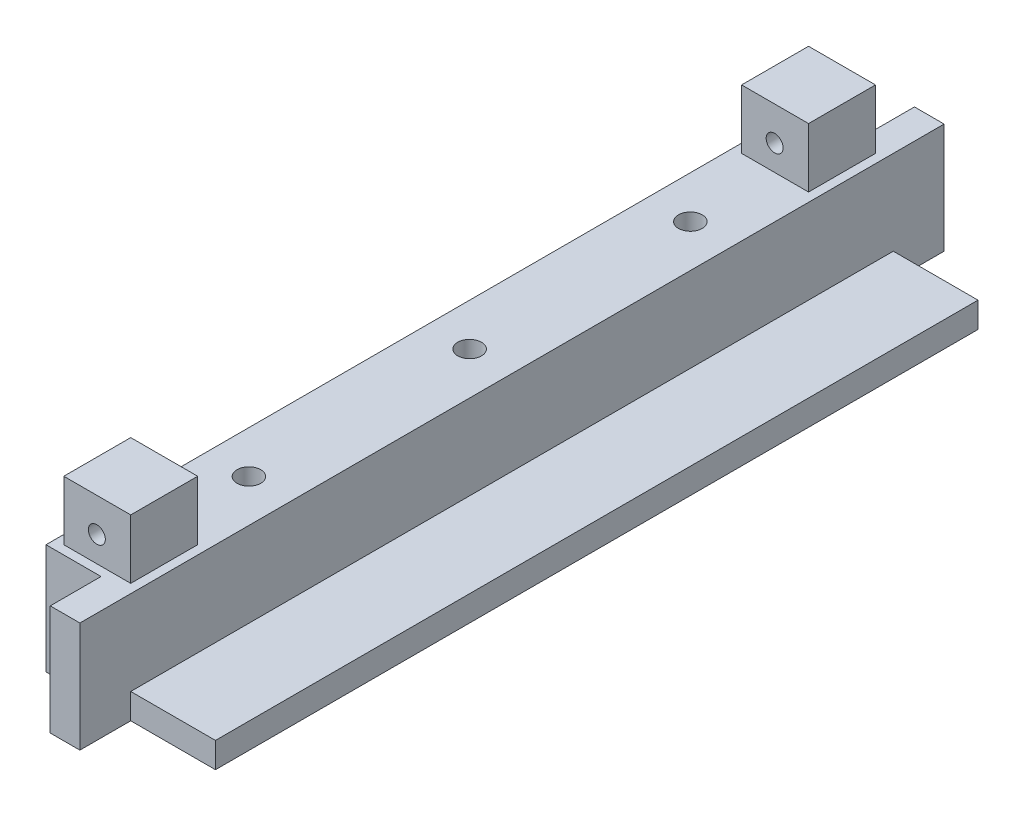
SolidWorks part; units mm, degrees
ref_plane "Płaszczyzna przednia" through (0, 0, 0) normal (0, 0, 1) x (1, 0, 0)
ref_plane "Płaszczyzna górna" through (0, 0, 0) normal (0, 1, 0) x (1, 0, 0)
ref_plane "Płaszczyzna prawa" through (0, 0, 0) normal (1, 0, 0) x (0, 0, -1)
sketch "Szkic1" plane through (0, 0, 0) normal (0, 0, 1) x (1, 0, 0)
  line L0 (10, -10) -> (10, -16)
  line L1 (-10, -10) -> (10, -10)
  line L2 (-10, -10) -> (-10, 10)
  line L3 (-10, 10) -> (10, 10)
  line L4 (10, -10) -> (10, 10)
  line L5 (-10, -10) -> (10, 10) construction
  line L6 (-10, 10) -> (10, -10) construction
  line L7 (10, -16) -> (-30, -16)
  line L8 (-30, -16) -> (-30, 10)
  line L9 (-30, 10) -> (-10, 10)
  point P0 (0, 0)
  dimension "D1" = 20
  dimension "D2" = 40
  dimension "D3" = 6
extrude "Dodanie-wyciągnięcie1" add sketch "Szkic1" along normal blind 180 contours L8 L7 L0 L1 L2 L3 region at (-16.25, -4.875, 0)
sketch "Szkic2" plane through (0, 10, 0) normal (0, 1, 0) x (1, 0, 0)
  line L0 (-30, -180) -> (-30, 0) construction
  line L1 (-12.1, -17.9) -> (-27.9, -17.9)
  line L2 (-12.1, -17.9) -> (-12.1, -2.1)
  line L3 (-12.1, -2.1) -> (-27.9, -2.1)
  line L4 (-27.9, -17.9) -> (-27.9, -2.1)
  line L5 (-12.1, -17.9) -> (-27.9, -2.1) construction
  line L6 (-12.1, -2.1) -> (-27.9, -17.9) construction
  line L7 (-30, 0) -> (-10, 0) construction
  point P0 (-20, -10)
  dimension "D1" = 15.8
  dimension "D2" = 15.8
  dimension "D3" = 10
  dimension "D4" = 10
extrude "Dodanie-wyciągnięcie2" add sketch "Szkic2" along normal blind 14
ref_plane "Płaszczyzna1" through (0, 0, 90) normal (0, 0, 1) x (1, 0, 0)
mirror "Lustro1" about plane through (0, 0, 90) normal (0, 0, 1) of "Dodanie-wyciągnięcie2"
sketch "Szkic5" plane through (0, 10, 0) normal (0, 1, 0) x (1, 0, 0)
  line L1 (-30, -180) -> (-10, -180) construction
  line L2 (-27.9, -162.1) -> (-12.1, -162.1) construction
  line L3 (-27.9, -17.9) -> (-12.1, -17.9) construction
  line L4 (-30, -180) -> (-30, 0) construction
  circle A0 centre (-20, -142.1) radius 2.8
  circle A1 centre (-20, -90) radius 2.8
  circle A2 centre (-20, -37.9) radius 2.8
  point P11 (-20, -180)
  point P17 (-30, -90)
  dimension "D1" = 5.6
  dimension "D4" = 20
  dimension "D5" = 20
extrude "Wytnij-wyciągnięcie2" cut sketch "Szkic5" against normal blind 10
sketch "Szkic6" plane through (0, 0, 177.9) normal (0, 0, 1) x (1, 0, 0)
  line L0 (-12.1, 24) -> (-27.9, 24) construction
  line L1 (-12.1, 24) -> (-12.1, 10) construction
  circle A0 centre (-20.1, 16) radius 2
  dimension "D1" = 4
  dimension "D2" = 8
  dimension "D3" = 8
extrude "Wytnij-wyciągnięcie3" cut sketch "Szkic6" against normal through all
sketch "Szkic9" plane through (0, 0, 180) normal (0, 0, 1) x (1, 0, 0)
  line L1 (-10, 10) -> (-17, 10)
  line L2 (-10, 10) -> (-10, -16)
  line L3 (-10, -16) -> (-17, -16)
  line L4 (-17, 10) -> (-17, -16)
  line L5 (10, -16) -> (-30, -16) construction
  dimension "D1" = 26
  dimension "D2" = 7
extrude "Dodanie-wyciągnięcie4" add sketch "Szkic9" along normal blind 12
sketch "Szkic10" plane through (-17, 0, 0) normal (-1, 0, 0) x (0, 0, 1)
  line L0 (192, 10) -> (180, 10) construction
  line L1 (180.9, 2.1) -> (191.1, 2.1)
  line L2 (180.9, 2.1) -> (180.9, -8.1)
  line L3 (180.9, -8.1) -> (191.1, -8.1)
  line L4 (191.1, 2.1) -> (191.1, -8.1)
  line L5 (180.9, 2.1) -> (191.1, -8.1) construction
  line L6 (180.9, -8.1) -> (191.1, 2.1) construction
  line L7 (192, 10) -> (192, -16) construction
  point P0 (186, -3)
  dimension "D1" = 10.2
  dimension "D2" = 13
  dimension "D3" = 6
extrude "Wytnij-wyciągnięcie4" cut sketch "Szkic10" against normal blind 2
ref_plane "Płaszczyzna2" through (0, 0, 90) normal (0, 0, 1) x (1, 0, 0)
mirror "Lustro2" about plane through (0, 0, 90) normal (0, 0, 1) of "Wytnij-wyciągnięcie4", "Dodanie-wyciągnięcie4"
